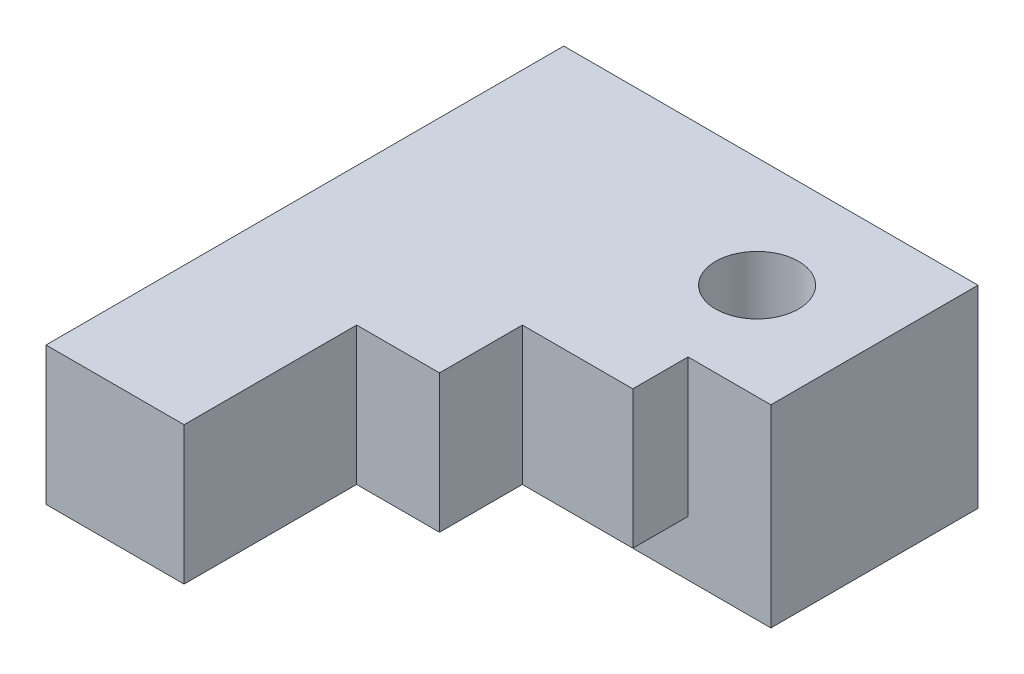
SolidWorks part; units mm, degrees
ref_plane "Front Plane" through (0, 0, 0) normal (0, 0, 1) x (1, 0, 0)
ref_plane "Top Plane" through (0, 0, 0) normal (0, 1, 0) x (1, 0, 0)
ref_plane "Right Plane" through (0, 0, 0) normal (1, 0, 0) x (0, 0, -1)
sketch "Sketch3" plane through (0, 0, 0) normal (0, 0, 1) x (1, 0, 0)
  line L0 (0, -20) -> (48, -20)
  line L1 (0, 0) -> (60, 0)
  line L2 (0, 0) -> (0, -28)
  line L3 (0, -28) -> (60, -28)
  line L4 (60, 0) -> (60, -28)
  line L5 (48, -20) -> (48, 0)
  line L6 (20, -20) -> (20, 0)
  line L7 (32, -20) -> (32, 0)
  dimension "D1" = 20
  dimension "D2" = 12
  dimension "D3" = 12
  dimension "D4" = 20
  dimension "D5" = 28
  dimension "D6" = 60
extrude "Boss-Extrude1" add sketch "Sketch3" along normal blind 30 contours L5 L0 L2 L3 L4 L1 region at (10, -20.6621, 0)
extrude "Boss-Extrude2" add sketch "Sketch3<3>" along normal blind 75 contours L0 L6 L1 L2 region at (10, -10, 0)
sketch "Sketch3<3>" plane through (0, 0, 0) normal (0, 0, 1) x (1, 0, 0) same geometry as "Sketch3"
extrude "Boss-Extrude3" add sketch "Sketch3<4>" along normal blind 50 contours L0 L7 L1 L6 region at (26, -10, 0)
sketch "Sketch3<4>" plane through (0, 0, 0) normal (0, 0, 1) x (1, 0, 0) same geometry as "Sketch3"
extrude "Boss-Extrude4" add sketch "Sketch3<5>" along normal blind 38 contours L7 L0 L5 L1 region at (40, -10, 0)
sketch "Sketch3<5>" plane through (0, 0, 0) normal (0, 0, 1) x (1, 0, 0) same geometry as "Sketch3"
sketch "Sketch4" plane through (0, -28, 0) normal (0, -1, 0) x (1, 0, 0)
  line L0 (60, 30) -> (60, 0) construction
  line L1 (0, 0) -> (60, 0) construction
  circle A0 centre (44, 16) radius 6
  dimension "D1" = 12
  dimension "D2" = 16
  dimension "D3" = 16
extrude "Cut-Extrude1" cut sketch "Sketch4" against normal through all
